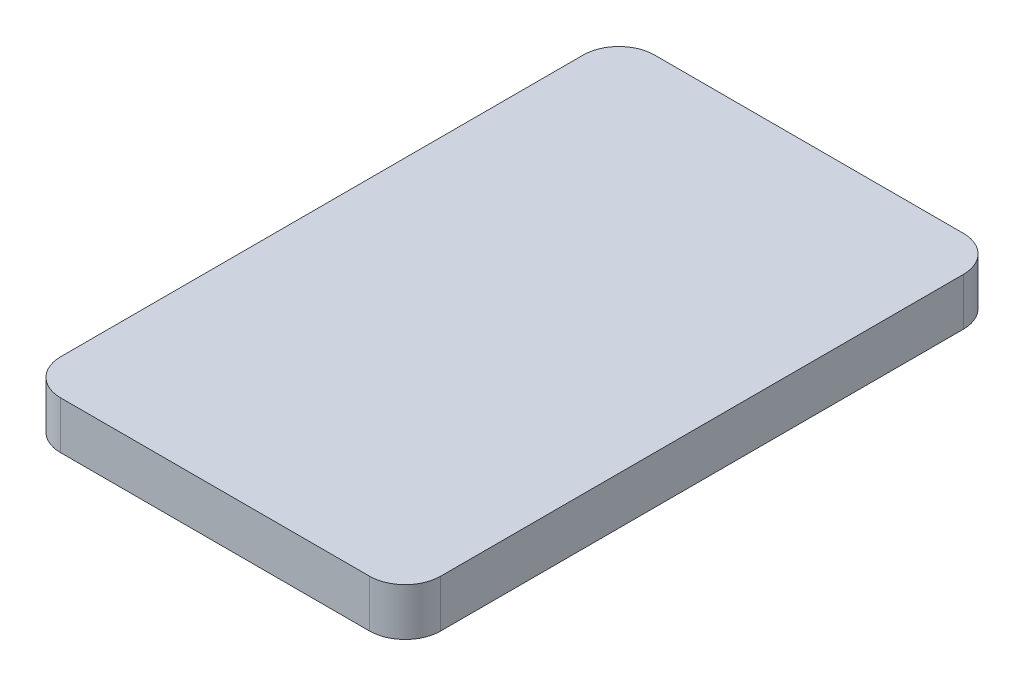
SolidWorks part; units mm, degrees
material "Plain Carbon Steel"
ref_plane "Front Plane" through (0, 0, 0) normal (0, 0, 1) x (1, 0, 0)
ref_plane "Top Plane" through (0, 0, 0) normal (0, 1, 0) x (1, 0, 0)
ref_plane "Right Plane" through (0, 0, 0) normal (1, 0, 0) x (0, 0, -1)
sketch "Sketch1" plane through (0, 0, 0) normal (0, 1, 0) x (1, 0, 0)
  line L0 (0, 0) -> (32, 0)
  line L1 (32, 0) -> (32, 50)
  line L4 (32, 50) -> (0, 50)
  line L7 (0, 50) -> (0, 0)
  dimension "D1" = 50
  dimension "D8" = 32
extrude "Boss-Extrude1" add sketch "Sketch1" along normal blind 4
fillet "Fillet1" radius 3 4 edges at (0, 2, -50) (32, 2, -50) (0, 2, 0) (32, 2, 0)
